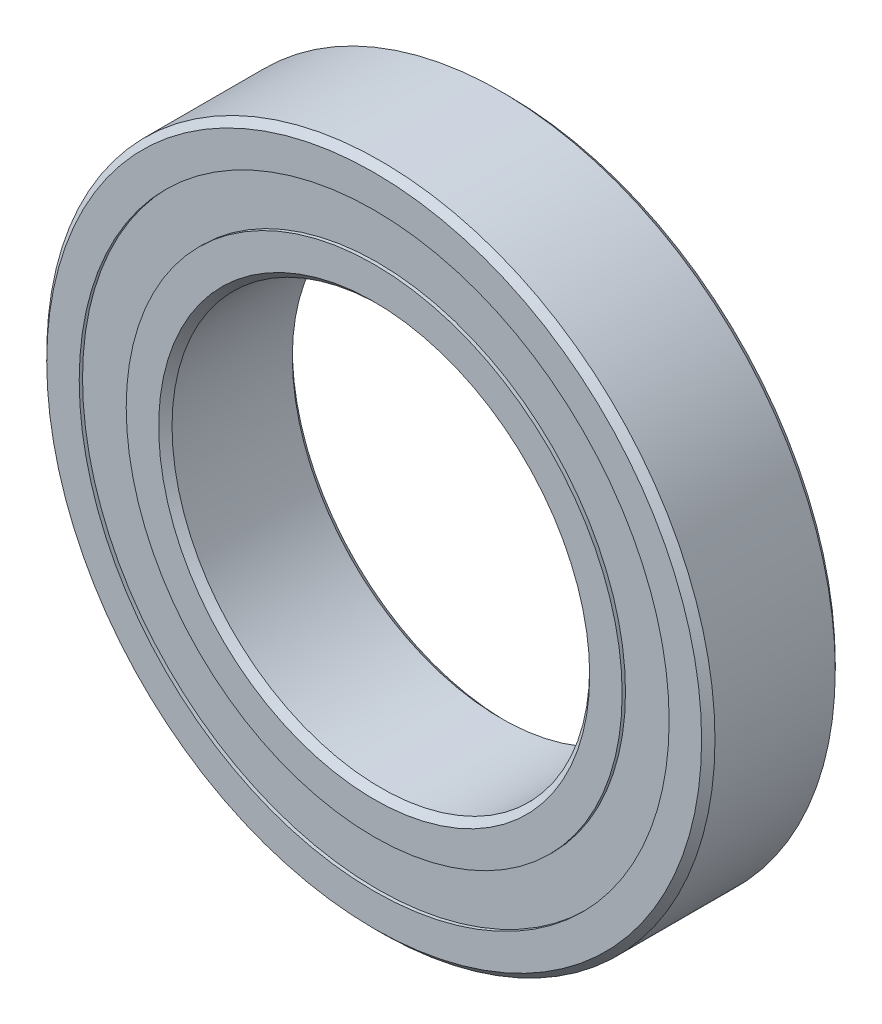
SolidWorks part; units mm, degrees
ref_plane "Front Plane" through (0, 0, 0) normal (0, 0, 1) x (1, 0, 0)
ref_plane "Top Plane" through (0, 0, 0) normal (0, 1, 0) x (1, 0, 0)
ref_plane "Right Plane" through (0, 0, 0) normal (1, 0, 0) x (0, 0, -1)
sketch "Sketch1" plane through (0, 0, 0) normal (1, 0, 0) x (0, 0, -1)
  line L0 (-8, 0) -> (8, 0) construction
  line L1 (0, 40) -> (0, -40) construction
  line L2 (7.2, 40) -> (-7.2, 40)
  line L3 (-7.2, 40) -> (-8, 39.2)
  line L4 (-8, 39.2) -> (-8, 35.3132)
  line L5 (-8, 35.3132) -> (-3.5556, 35.3132)
  line L6 (8, 35.3132) -> (3.5556, 35.3132)
  line L7 (8, 39.2) -> (8, 35.3132)
  line L8 (7.2, 40) -> (8, 39.2)
  line L9 (0, 40) -> (0, 32.5) construction
  line L10 (0, 32.5) -> (0, 25) construction
  arc A0 (-3.5556, 35.3132) -> (3.5556, 35.3132) centre (0, 32.5) cw
  point P14 (0, 25)
  dimension "Width" = 16
  dimension "OD" = 80
  dimension "D1" = 45
  dimension "D2" = 0.8
  dimension "Shaft Dia" = 50
  dimension "D3" = 7.1111
  dimension "D4" = 2.8132
revolve "Revolve1" add sketch "Sketch1" angle 360 about L0
sketch "Sketch3" plane through (0, 0, 0) normal (1, 0, 0) x (0, 0, -1)
  line L0 (-8, 29.6868) -> (-3.5556, 29.6868)
  line L1 (0, 40) -> (0, -40) construction
  line L2 (-8, 39.2) -> (-8, 35.3132) construction
  line L3 (-8, 29.6868) -> (-8, 25.8)
  line L4 (-7.2, 40) -> (-8, 39.2) construction
  line L5 (-8, 25.8) -> (-7.2, 25)
  line L6 (-7.2, 25) -> (7.2, 25)
  line L7 (7.2, 40) -> (7.2, -40) construction
  line L8 (7.2, 25) -> (8, 25.8)
  line L9 (8, -39.2) -> (8, 39.2) construction
  line L10 (8, 25.8) -> (8, 29.6868)
  line L11 (8, 29.6868) -> (3.5556, 29.6868)
  line L13 (7.2, 40) -> (8, 39.2) construction
  arc A0 (3.5556, 35.3132) -> (-3.5556, 35.3132) centre (0, 32.5) ccw construction
  arc A1 (3.5556, 29.6868) -> (-3.5556, 29.6868) centre (0, 32.5) cw
revolve "Revolve3" add sketch "Sketch3" angle 360 about L0
sketch "Sketch4" plane through (0, 0, 0) normal (1, 0, 0) x (0, 0, -1)
  line L0 (-4.5339, 32.5) -> (4.5339, 32.5)
  arc A2 (-4.5339, 32.5) -> (4.5339, 32.5) centre (0, 32.5) cw
  arc A3 (3.5556, 35.3132) -> (-3.5556, 35.3132) centre (0, 32.5) ccw construction
revolve "Revolve4" add sketch "Sketch4" angle 360 about L0
ref_axis "Axis1" through (0, 0, -8) along (0, 0, 1)
pattern_circular "CirPattern1" count 12 every 30 about axis through (0, 0, -8) along (0, 0, 1) of bodies 104
sketch "Sketch5" plane through (0, 0, 0) normal (1, 0, 0) x (0, 0, -1)
  line L0 (-8, 35.3132) -> (-3.5556, 35.3132) construction
  line L1 (-7.6, 35.3132) -> (-4.5339, 35.3132)
  line L2 (-7.6, 35.3132) -> (-7.6, 29.6868)
  line L3 (-7.6, 29.6868) -> (-4.5339, 29.6868)
  line L4 (-4.5339, 35.3132) -> (-4.5339, 29.6868)
  line L5 (-8, 29.6868) -> (-3.5556, 29.6868) construction
  line L6 (8, 35.3132) -> (3.5556, 35.3132) construction
  line L7 (7.6, 35.3132) -> (4.5339, 35.3132)
  line L8 (7.6, 35.3132) -> (7.6, 29.6868)
  line L9 (7.6, 29.6868) -> (4.5339, 29.6868)
  line L10 (4.5339, 35.3132) -> (4.5339, 29.6868)
  line L11 (8, 29.6868) -> (3.5556, 29.6868) construction
  line L12 (-7.2, 40) -> (-8, 39.2) construction
  point P18 (-7.6, 39.6)
revolve "Revolve5" add sketch "Sketch5" angle 360 about L0
equation "\"D2@Sketch1\" = \"Width@Sketch1\"*.05"
equation "\"D3@Sketch1\" = \"Width@Sketch1\"/2.25"
equation "\"D4@Sketch1\" = (((\"OD@Sketch1\"-\"Width@Sketch1\")/2)/3.25)/3.5"
equation "\"D2@CirPattern1\" = 360/\"Balls@CirPattern1\""
